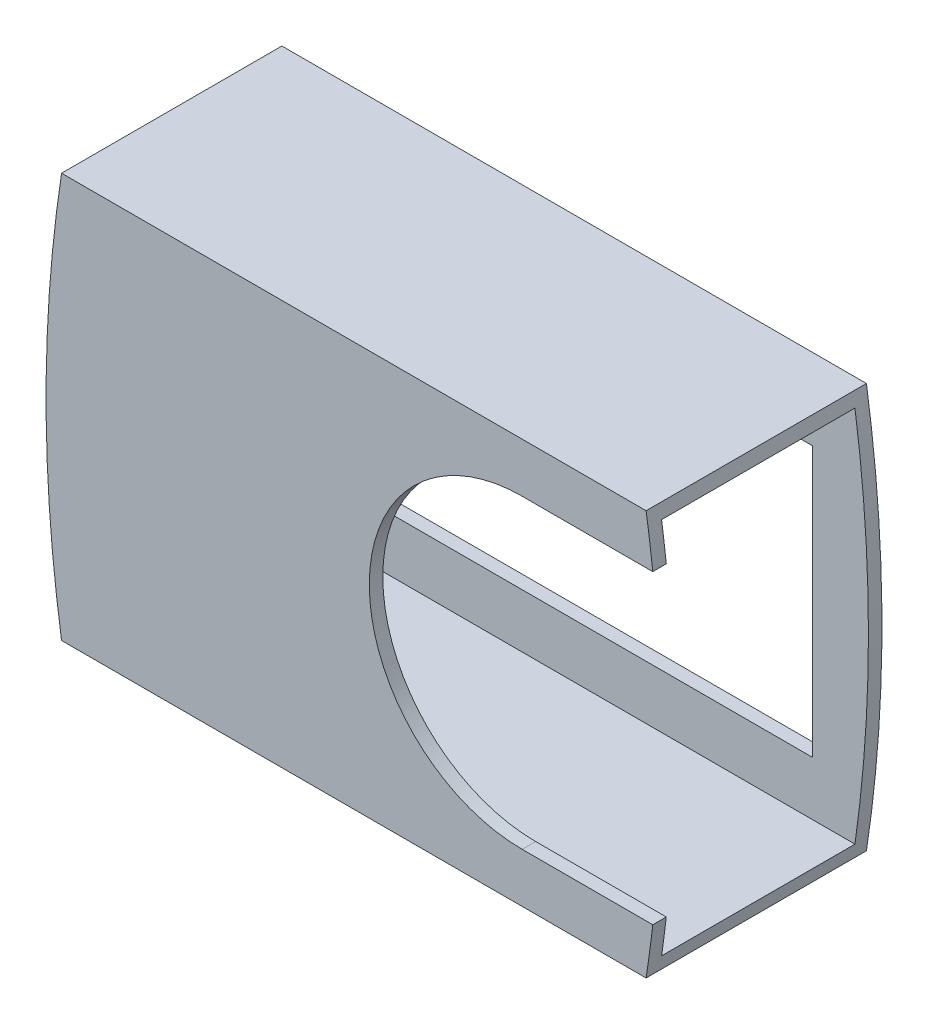
SolidWorks part; units mm, degrees
ref_plane "Alzado" through (0, 0, 0) normal (0, 0, 1) x (1, 0, 0)
ref_plane "Planta" through (0, 0, 0) normal (0, 1, 0) x (1, 0, 0)
ref_plane "Vista lateral" through (0, 0, 0) normal (1, 0, 0) x (0, 0, -1)
sketch "Croquis1" plane through (0, 0, 0) normal (0, 0, 1) x (1, 0, 0)
  line L0 (0, 0) -> (-62, 0)
  line L1 (-62, 42) -> (0, 42)
  line L2 (-62, 42) -> (-62, 0) construction
  line L3 (-62, 21) -> (-63.5, 21) construction
  line L4 (0, 42) -> (0, 21) construction
  line L5 (0, 21) -> (1.5, 21) construction
  line L6 (-63.5, 43.5) -> (1.5, 43.5)
  line L7 (-63.5, -1.5) -> (1.5, -1.5)
  arc A0 (-62, 42) -> (-62, 0) centre (84.5026, 21) ccw
  arc A1 (0, 42) -> (0, 0) centre (-146.5026, 21) cw
  arc A2 (-63.5, 43.5) -> (-63.5, -1.5) centre (82.7797, 21) ccw
  arc A3 (1.5, 43.5) -> (1.5, -1.5) centre (-144.7797, 21) cw
  dimension "D3" = 1.5
  dimension "D5" = 65
  dimension "D1" = 62
  dimension "D2" = 42
  dimension "D4" = 1.5
  dimension "D6" = 1.5
  dimension "D7" = 1.5
  dimension "D8" = 65
extrude "Saliente-Extruir1" add sketch "Croquis1" along normal blind 21.5
sketch "Croquis2" plane through (0, 0, 21.5) normal (0, 0, 1) x (1, 0, 0)
  line L0 (-63.5, 43.5) -> (1.5, 43.5)
  line L1 (1.5, -1.5) -> (-63.5, -1.5)
  arc A0 (-63.5, 43.5) -> (-63.5, -1.5) centre (82.7797, 21) ccw
  arc A1 (1.5, 43.5) -> (1.5, -1.5) centre (-144.7797, 21) cw
extrude "Saliente-Extruir2" add sketch "Croquis2" along normal blind 1.5
sketch "Croquis3" plane through (0, 0, 0) normal (0, 0, -1) x (-1, 0, 0)
  line L0 (-1.5, 43.5) -> (63.5, 43.5)
  line L1 (-1.5, -1.5) -> (63.5, -1.5)
  line L2 (0, 42) -> (62, 42) construction
  line L3 (3, 36) -> (53, 36)
  line L4 (3, 36) -> (3, 6)
  line L5 (3, 6) -> (53, 6)
  line L6 (53, 36) -> (53, 6)
  line L7 (62, 0) -> (0, 0) construction
  arc A0 (-1.5, 43.5) -> (-1.5, -1.5) centre (144.7797, 21) ccw
  arc A1 (63.5, 43.5) -> (63.5, -1.5) centre (-82.7797, 21) cw
  dimension "D1" = 6
  dimension "D2" = 6
  dimension "D3" = 3
  dimension "D4" = 50
extrude "Saliente-Extruir3" add sketch "Croquis3" along normal blind 1.5
sketch "Croquis4" plane through (0, 0, 23) normal (0, 0, 1) x (1, 0, 0)
  line L0 (3.2203, 21) -> (-23.7797, 21) construction
  line L1 (-23.7797, 21) -> (-12.2797, 21) construction
  line L4 (-12.2797, 38) -> (2.2407, 38)
  line L5 (-12.2797, 4) -> (2.2407, 4)
  arc A0 (1.5, -1.5) -> (1.5, 43.5) centre (-144.7797, 21) ccw construction
  arc A3 (-12.2797, 38) -> (-12.2797, 4) centre (-12.2797, 21) ccw
  arc A4 (2.2407, 38) -> (2.2407, 4) centre (-144.7797, 21) cw
  dimension "D3" = 17
  dimension "D1" = 27
  dimension "D2" = 11.5
extrude "Cortar-Extruir1" cut sketch "Croquis4" against normal blind 1.5
ref_plane "Plano2" through (1.5, 0, 0) normal (-1, 0, 0) x (0, 0, 1)
sketch "Croquis7" plane through (1.5, 0, 0) normal (-1, 0, 0) x (0, 0, 1)
  line L0 (23, 43.5) -> (-1.5, 43.5) construction
  line L1 (21.5, 42) -> (0, 42)
  line L2 (21.5, 42) -> (21.5, 0)
  line L3 (21.5, 0) -> (0, 0)
  line L4 (0, 42) -> (0, 0)
  line L5 (23, -1.5) -> (-1.5, -1.5) construction
  dimension "D1" = 1.5
  dimension "D2" = 1.5
  dimension "D3" = 1.5
  dimension "D4" = 1.5
extrude "Cortar-Extruir2" cut sketch "Croquis7" against normal blind 3 and the other way blind 1.5
ref_plane "Plano4" through (-63.5, 0, 0) normal (-1, 0, 0) x (0, 0, 1)
sketch "Croquis8" plane through (-63.5, 0, 0) normal (-1, 0, 0) x (0, 0, 1)
  line L0 (23, 43.5) -> (-1.5, -1.5) construction
  circle A0 centre (10.75, 21) radius 8
extrude "Cortar-Extruir3" cut sketch "Croquis8" against normal blind 10 and the other way blind 10
